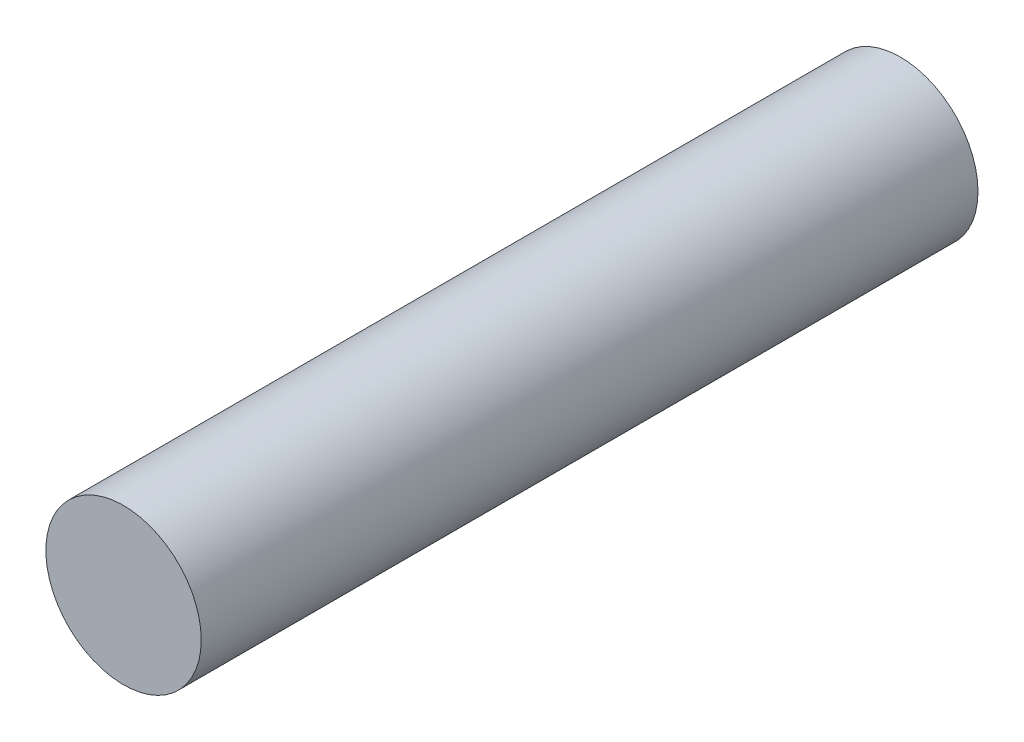
SolidWorks part; units mm, degrees
ref_plane "정면" through (0, 0, 0) normal (0, 0, 1) x (1, 0, 0)
ref_plane "윗면" through (0, 0, 0) normal (0, 1, 0) x (1, 0, 0)
ref_plane "우측면" through (0, 0, 0) normal (1, 0, 0) x (0, 0, -1)
sketch "스케치2" plane through (0, 0, 0) normal (0, 0, 1) x (1, 0, 0)
  circle A0 centre (0, 0) radius 4
  circle A1 centre (0, 0) radius 8
  dimension "D1" = 8
  dimension "D2" = 16
extrude "보스-돌출1" add sketch "스케치2" along normal blind 80 contours A1
extrude "컷-돌출1" cut sketch "스케치2<3>" along normal blind 30 contours A0 region at (0, 0, 0)
sketch "스케치2<3>" plane through (0, 0, 0) normal (0, 0, 1) x (1, 0, 0) same geometry as "스케치2"
